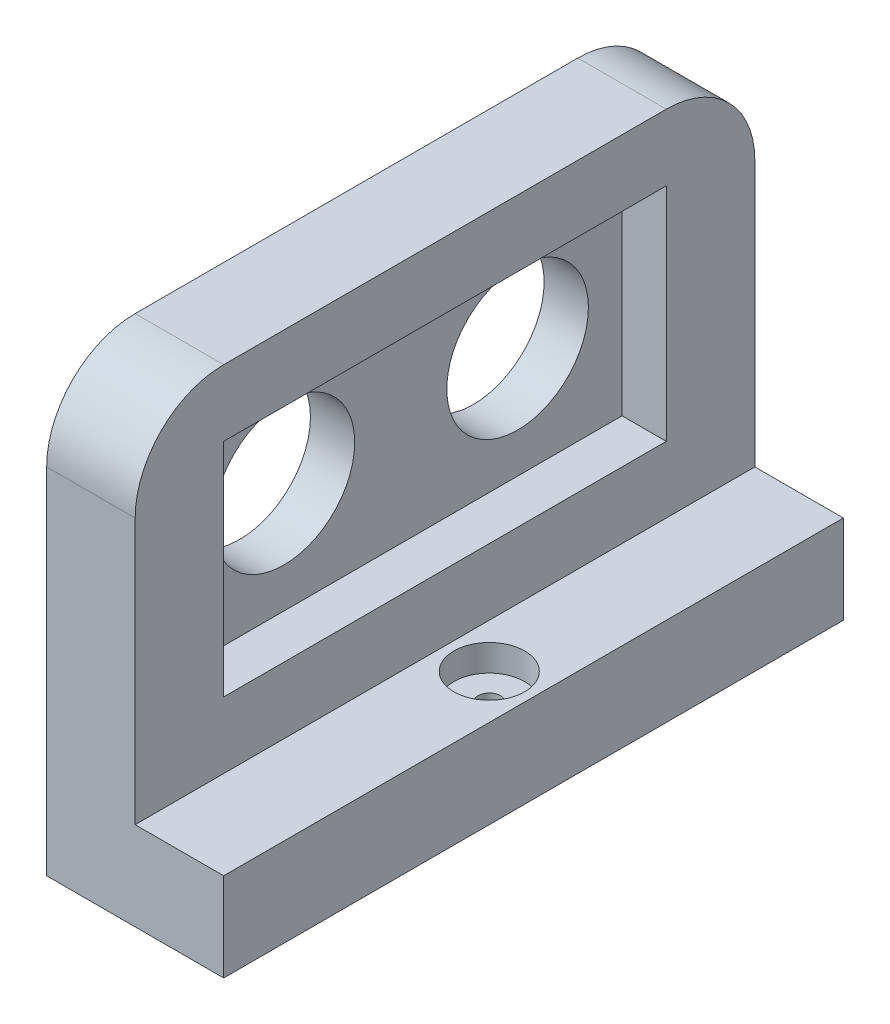
SolidWorks part; units mm, degrees
ref_plane "Front Plane" through (0, 0, 0) normal (0, 0, 1) x (1, 0, 0)
ref_plane "Top Plane" through (0, 0, 0) normal (0, 1, 0) x (1, 0, 0)
ref_plane "Right Plane" through (0, 0, 0) normal (1, 0, 0) x (0, 0, -1)
sketch "Sketch1" plane through (0, 0, 0) normal (0, 0, 1) x (1, 0, 0)
  line L0 (0, 0) -> (0, 10)
  line L1 (0, 10) -> (-10, 10)
  line L2 (-10, 10) -> (-10, 50)
  line L3 (-10, 50) -> (-20, 50)
  line L4 (-20, 50) -> (-20, 0)
  line L5 (-20, 0) -> (0, 0)
  dimension "D1" = 50
  dimension "D2" = 10
  dimension "D3" = 10
  dimension "D4" = 10
extrude "Boss-Extrude1" add sketch "Sketch1" along normal blind 70 contours L4 L5 L0 L1 L2 L3
sketch "Sketch2" plane through (-10, 0, 0) normal (1, 0, 0) x (0, 0, -1)
  line L0 (-31.1498, 42.5) -> (-31.1498, 50) construction
  line L1 (-60, 42.5) -> (-10, 42.5)
  line L2 (-60, 42.5) -> (-60, 17.5)
  line L3 (-60, 17.5) -> (-10, 17.5)
  line L4 (-10, 42.5) -> (-10, 17.5)
  line L5 (-70, 50) -> (0, 50) construction
  line L6 (-26.3251, 17.5) -> (-26.3251, 10) construction
  line L7 (-70, 10) -> (0, 10) construction
  line L8 (-10, 28.025) -> (0, 28.025) construction
  line L9 (0, 10) -> (0, 50) construction
  line L10 (-60, 26.6465) -> (-70, 26.6465) construction
  line L11 (-70, 10) -> (-70, 50) construction
  line L13 (-40.2, 30) -> (-29.8, 30) construction
  line L14 (-13.8, 30) -> (-10, 30) construction
  line L15 (-56.2, 30) -> (-60, 30) construction
  circle A0 centre (-48.2, 30) radius 8
  circle A1 centre (-21.8, 30) radius 8
  point P30 (0, 0)
  dimension "D3" = 16
  dimension "D4" = 16
  dimension "D1" = 50
  dimension "D2" = 25
  dimension "D5" = 10.4
extrude "Cut-Extrude9" cut sketch "Sketch2" against normal through all contours A0
extrude "Cut-Extrude10" cut sketch "Sketch2<12>" against normal through all contours A1
sketch "Sketch2<12>" plane through (-10, 0, 0) normal (1, 0, 0) x (0, 0, -1) same geometry as "Sketch2"
extrude "Cut-Extrude12" cut sketch "Sketch2<14>" against normal blind 5 contours L1 L4 L3 L2
sketch "Sketch2<14>" plane through (-10, 0, 0) normal (1, 0, 0) x (0, 0, -1) same geometry as "Sketch2"
sketch "Sketch3" plane through (0, 10, 0) normal (0, 1, 0) x (1, 0, 0)
  line L0 (-5, 0) -> (-5, -70) construction
  line L1 (0, 0) -> (-10, 0) construction
  line L2 (0, -70) -> (-10, -70) construction
  circle A0 centre (-5, -35) radius 4
  circle A1 centre (-5, -35) radius 1.25
  dimension "D1" = 8
  dimension "D2" = 2.5
extrude "Cut-Extrude13" cut sketch "Sketch3" against normal blind 3
extrude "Cut-Extrude14" cut sketch "Sketch3<2>" against normal through all contours A1
sketch "Sketch3<2>" plane through (0, 10, 0) normal (0, 1, 0) x (1, 0, 0) same geometry as "Sketch3"
fillet "Fillet1" radius 10 1 edges at (-15, 50, 70) type face fillet first side face at (-15, 50, 35) second side face at (-10, 20, 70)
fillet "Fillet2" radius 10 1 edges at (-15, 50, 0) type face fillet first side face at (-15, 50, 30) second side face at (-10, 20, 0)
